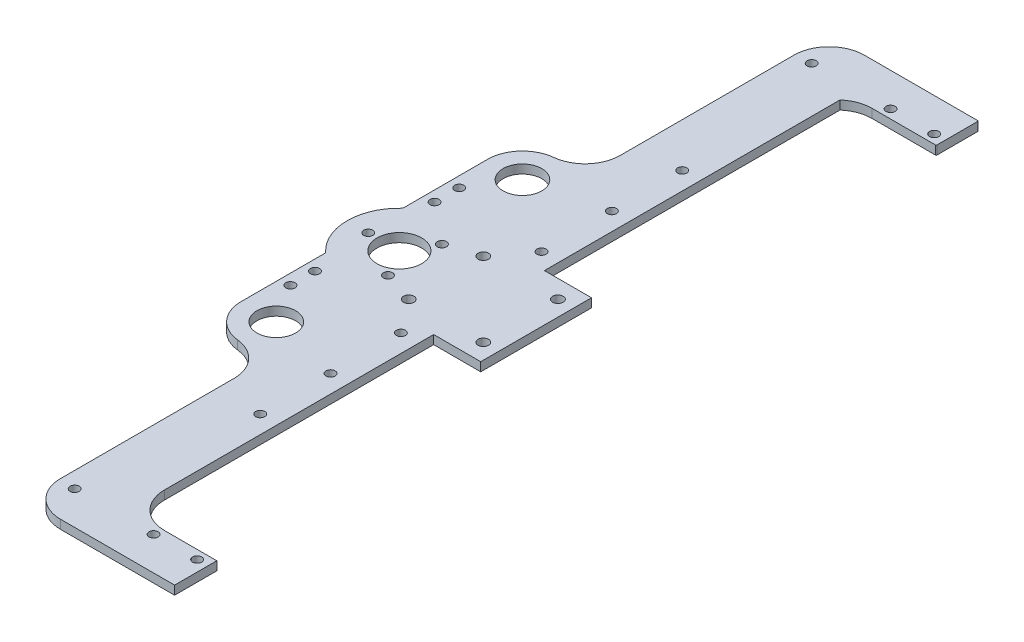
SolidWorks part; units mm, degrees
ref_plane "Front Plane" through (0, 0, 0) normal (0, 0, 1) x (1, 0, 0)
ref_plane "Top Plane" through (0, 0, 0) normal (0, 1, 0) x (1, 0, 0)
ref_plane "Right Plane" through (0, 0, 0) normal (1, 0, 0) x (0, 0, -1)
sketch "Sketch1" plane through (0, 0, 0) normal (0, 1, 0) x (1, 0, 0)
  line L0 (-67.9713, -52.7283) -> (-67.9713, -82.5864)
  line L6 (-67.9713, 4.9919) -> (-67.9713, -24.8662)
  line L14 (-22.9035, 106.3552) -> (-32.5284, 106.3552)
  line L17 (8.6823, 106.3552) -> (-7.1106, 106.3552)
  line L20 (-32.5284, -183.9497) -> (7.3984, -183.9497)
  line L22 (-22.9035, 106.3552) -> (8.6823, 106.3552)
  line L24 (-14.5158, 91.1152) -> (8.6823, 91.1152)
  line L26 (7.3984, -183.9497) -> (8.6823, -183.9497)
  line L28 (-10.2035, -168.7097) -> (8.6823, -168.7097)
  line L30 (8.6823, -168.7097) -> (8.6823, -183.9497)
  line L31 (-45.2284, -108.5097) -> (-45.2284, -171.2497)
  line L32 (8.6823, 106.3552) -> (8.6823, 91.1152)
  line L33 (-45.2284, 93.6552) -> (-45.2284, 30.9152)
  line L34 (-22.9035, -156.0097) -> (-22.9035, -58.7973)
  line L35 (-22.9035, -38.7973) -> (-5.9035, -38.7973) construction
  line L37 (-22.9035, -58.7973) -> (-22.9035, -64.1973)
  line L40 (-5.9035, -38.7973) -> (-5.9035, -18.7973)
  line L41 (-5.9035, -38.7973) -> (-5.9035, -58.7973)
  line L42 (-5.9035, -18.7973) -> (-22.9035, -18.7973)
  line L43 (-5.9035, -58.7973) -> (-22.9035, -58.7973)
  line L44 (-22.9035, -18.7973) -> (-22.9035, 87.9512)
  arc A0 (-67.9713, -82.5864) -> (-56.6084, -95.8785) centre (-55.2885, -83.2473) ccw
  arc A1 (-45.2284, -108.5097) -> (-56.6084, -95.8785) centre (-57.9284, -108.5097) ccw
  arc A4 (-56.6084, 18.284) -> (-45.2284, 30.9152) centre (-57.9284, 30.9152) ccw
  arc A5 (-56.6084, 18.284) -> (-67.9713, 4.9919) centre (-55.2885, 5.6527) ccw
  arc A6 (-67.9713, -24.8662) -> (-67.9713, -52.7283) centre (-55.2885, -38.7973) ccw
  arc A22 (-45.2284, 93.6552) -> (-32.5284, 106.3552) centre (-32.5284, 93.6552) cw
  arc A23 (-45.2284, -171.2497) -> (-32.5284, -183.9497) centre (-32.5284, -171.2497) ccw
  arc A24 (-22.9035, 87.9512) -> (-14.5158, 91.1152) centre (-14.5158, 78.4152) cw
  arc A25 (-22.9035, -156.0097) -> (-10.2035, -168.7097) centre (-10.2035, -156.0097) ccw
  circle A30 centre (-55.2885, -83.2473) radius 6.985 construction
  circle A31 centre (-64.1613, -69.2773) radius 1.65 construction
  circle A32 centre (-64.1613, -60.3873) radius 1.65 construction
  circle A33 centre (-55.2885, -38.7973) radius 8.0645 construction
  circle A34 centre (-49.6688, -29.0636) radius 1.65 construction
  circle A35 centre (-49.6688, -48.531) radius 1.65 construction
  circle A36 centre (-66.528, -38.7973) radius 1.65 construction
  circle A37 centre (-64.1613, -17.2073) radius 1.65 construction
  circle A38 centre (-64.1613, -8.3173) radius 1.65 construction
  circle A39 centre (-55.2885, 5.6527) radius 6.985 construction
  circle A40 centre (-55.2885, -83.2473) radius 6.985
  circle A41 centre (-64.1613, -69.2773) radius 1.65
  circle A42 centre (-64.1613, -60.3873) radius 1.65
  circle A43 centre (-55.2885, -38.7973) radius 8.0645
  circle A44 centre (-49.6688, -29.0636) radius 1.65
  circle A45 centre (-49.6688, -48.531) radius 1.65
  circle A46 centre (-66.528, -38.7973) radius 1.65
  circle A47 centre (-64.1613, -17.2073) radius 1.65
  circle A48 centre (-64.1613, -8.3173) radius 1.65
  circle A49 centre (-55.2885, 5.6527) radius 6.985
  circle A50 centre (-29.342, 37.4027) radius 1.65 construction
  circle A51 centre (-29.342, 12.0027) radius 1.65 construction
  circle A52 centre (-29.342, -13.3973) radius 1.65 construction
  circle A54 centre (-29.342, -64.1973) radius 1.65 construction
  circle A55 centre (-29.342, -89.5973) radius 1.65 construction
  circle A56 centre (-29.342, -114.9973) radius 1.65 construction
  circle A57 centre (-29.342, 37.4027) radius 1.65
  circle A58 centre (-29.342, 12.0027) radius 1.65
  circle A59 centre (-29.342, -13.3973) radius 1.65
  circle A61 centre (-29.342, -64.1973) radius 1.65
  circle A62 centre (-29.342, -89.5973) radius 1.65
  circle A63 centre (-29.342, -114.9973) radius 1.65
  point P58 (-45.2284, 106.3552)
  dimension "D5" = 15.24
  dimension "D6" = 15.24
  dimension "D7" = 62.74
  dimension "D8" = 62.74
  dimension "D44" = 12.7
  dimension "D46" = 12.7
  dimension "D47" = 12.7
  dimension "D1" = 17
  dimension "D2" = 20
  dimension "D36" = 22.3249
extrude "Boss-Extrude1" add sketch "Sketch1" along normal blind 3.175 contours A25 A24 L24 L32 L17 L22 L14 A22 A4 A5 L6 A6 L0 A0 A1 A23 L20 L26 L30 L28 A63 A62 A61 A59 A58 A57 A49 A48 A47 A46 region at (-34.9503, 0, 39.1232)
fillet "Fillet2" radius 0.254 2 edges at (8.6823, 1.5875, -91.1152) (8.6823, 1.5875, -106.3552)
sketch "Sketch4" plane through (0, 3.175, 0) normal (0, 1, 0) x (1, 0, 0)
  circle A0 centre (4.754, 94.2902) radius 1.65
  circle A1 centre (-10.971, 94.2902) radius 1.65
  circle A2 centre (-39.471, 94.2902) radius 1.65
  circle A3 centre (-39.471, -171.8847) radius 1.65
  circle A4 centre (-10.971, -171.8847) radius 1.65
  circle A5 centre (4.754, -171.8847) radius 1.65
  dimension "D1" = 3.3
extrude "Cut-Extrude1" cut sketch "Sketch4" against normal through all
sketch "Sketch5" plane through (0, 3.175, 0) normal (0, 1, 0) x (1, 0, 0)
  circle A1 centre (-11.5006, -25.3269) radius 1.8986
  circle A2 centre (-38.4414, -25.3269) radius 1.8986
  circle A5 centre (-38.4414, -52.2677) radius 1.8986
  circle A6 centre (-11.5006, -52.2677) radius 1.8986
  point P9 (-38.4414, -52.2677)
  point P17 (-11.5006, -52.2677)
  point P18 (-11.5006, -25.3269)
  point P19 (-38.4414, -52.2677)
  dimension "D1" = 3.7973
extrude "Cut-Extrude2" cut sketch "Sketch5" against normal through all
